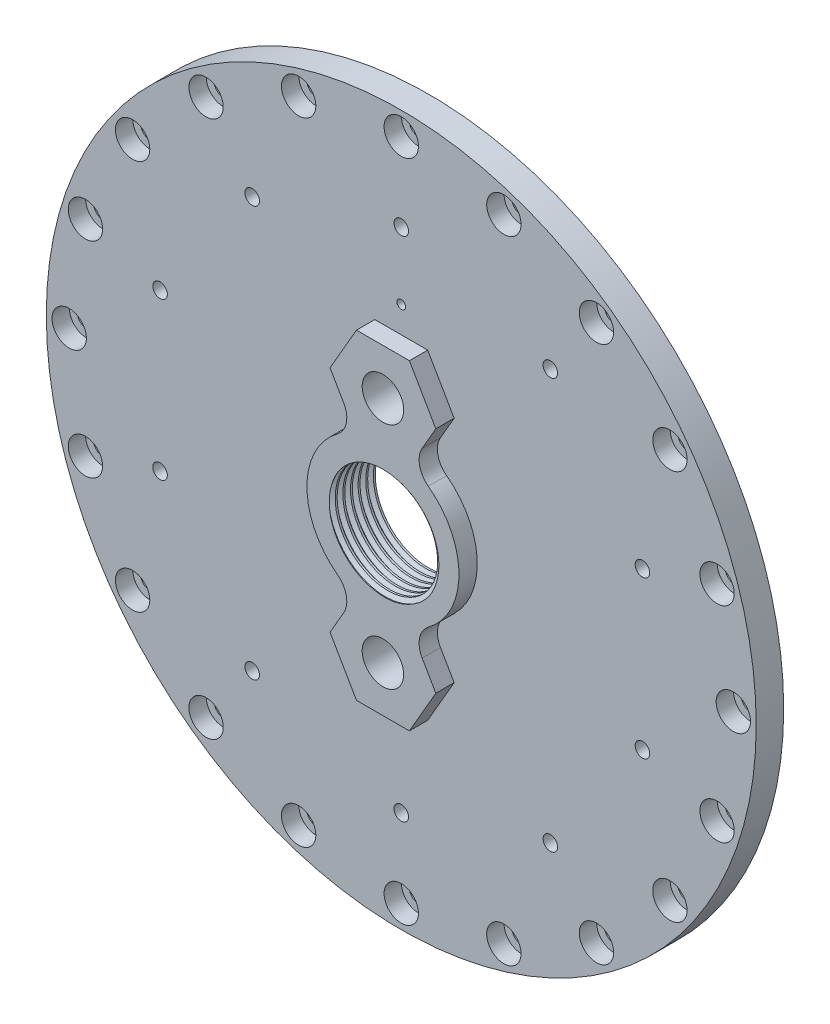
SolidWorks part; units mm, degrees
material "AISI 316 Stainless Steel Sheet (SS)"
ref_plane "Front Plane" through (0, 0, 0) normal (0, 0, 1) x (1, 0, 0)
ref_plane "Top Plane" through (0, 0, 0) normal (0, 1, 0) x (1, 0, 0)
ref_plane "Right Plane" through (0, 0, 0) normal (1, 0, 0) x (0, 0, -1)
sketch "Sketch1" plane through (0, 0, 0) normal (1, 0, 0) x (0, 0, -1)
  line L0 (0, 21.082) -> (0, 98.425)
  line L1 (0, 98.425) -> (7.62, 98.425)
  line L2 (7.62, 98.425) -> (7.62, 88.6333)
  line L3 (7.62, 83.82) -> (5.08, 83.82)
  line L4 (5.08, 83.82) -> (5.08, 56.8325)
  line L5 (5.08, 56.8325) -> (7.62, 56.8325)
  line L6 (7.62, 56.8325) -> (7.62, 53.0225)
  line L7 (7.62, 14.732) -> (-5.08, 14.732)
  line L8 (-5.08, 14.732) -> (-5.08, 21.082)
  line L9 (-5.08, 21.082) -> (0, 21.082)
  line L10 (0, 0) -> (59.2702, 0) construction
  line L12 (7.62, 49.6951) -> (6.2992, 49.6951)
  line L14 (7.62, 47.0535) -> (6.2992, 47.0535)
  line L15 (6.2992, 49.6951) -> (6.2992, 47.0535)
  line L20 (7.62, 47.0535) -> (7.62, 46.0375)
  line L21 (7.62, 85.1027) -> (7.62, 83.82)
  line L22 (7.62, 50.4825) -> (7.62, 49.6951)
  line L23 (7.62, 21.59) -> (7.62, 14.732)
  line L24 (7.62, 46.0375) -> (5.08, 46.0375)
  line L26 (7.62, 21.59) -> (5.08, 21.59)
  line L27 (5.08, 46.0375) -> (5.08, 21.59)
  line L28 (7.62, 53.0225) -> (6.35, 53.0225)
  line L32 (7.62, 50.4825) -> (6.35, 50.4825)
  line L33 (6.35, 53.0225) -> (6.35, 50.4825)
  line L35 (7.62, 88.6333) -> (5.6642, 88.6333)
  line L37 (7.62, 85.1027) -> (5.6642, 85.1027)
  line L38 (5.6642, 88.6333) -> (5.6642, 85.1027)
  point P19 (6.35, 51.7525)
  point P22 (6.2992, 48.3743)
  point P31 (5.6642, 86.868)
  dimension "D1" = 196.85
  dimension "D2" = 2.54
  dimension "D3" = 7.62
  dimension "D4" = 2.54
  dimension "D5" = 113.665
  dimension "D6" = 12.7
  dimension "D7" = 29.464
  dimension "D8" = 6.35
  dimension "D9" = 2.6416
  dimension "D10" = 96.7486
  dimension "D11" = 1.3208
  dimension "D12" = 167.64
  dimension "D13" = 92.075
  dimension "D14" = 43.18
  dimension "D15" = 1.27
  dimension "D16" = 2.54
  dimension "D17" = 103.505
  dimension "D18" = 1.9558
  dimension "D19" = 3.5306
  dimension "D20" = 173.736
revolve "Revolve1" add sketch "Sketch1" angle 360 about L10 region at (0, 54.7882, -2.7116)
thread "Thread1" pitch 2.1167 method cut profile "Thread Profile1" start angle 0, offset 4.318, length 0, pitch 2.1167, diameter 29.464
ref_plane "Plane1" through (-14.732, 0, 9.398) normal (0, -1, 0) x (-1, 0, 0)
sketch "Thread Profile1" plane through (-14.732, 0, 9.398) normal (0, -1, 0) x (-1, 0, 0)
  line L0 (0, 0) -> (0, 2.1167) construction
  line L1 (0, 0) -> (1.1457, 0.6615)
  line L2 (1.1457, 0.6615) -> (1.1457, 0.926)
  line L3 (1.1457, 0.926) -> (0, 1.5875)
  line L4 (1.1457, 0.7937) -> (0, 0.7937) construction
  line L11 (0, 0) -> (0, 1.5875)
  point P2 (0, 0)
  dimension "Pitch" = 2.1167
  dimension "Profile_Angle" = 60
  dimension "Profile_Land" = 0.2646
  dimension "Profile_Height" = 1.1457
sketch "Sketch15" plane through (0, 0, 0) normal (0, 0, 1) x (1, 0, 0)
  line L10 (0, 0) -> (104.8126, 0) construction
  line L11 (7.3323, 19.05) -> (14.6647, 31.75)
  line L12 (14.6647, 31.75) -> (7.3323, 44.45)
  line L13 (7.3323, 44.45) -> (-7.3323, 44.45)
  line L14 (-7.3323, 44.45) -> (-14.6647, 31.75)
  line L15 (-14.6647, 31.75) -> (-7.3323, 19.05)
  line L16 (-7.3323, 19.05) -> (7.3323, 19.05)
  line L17 (-7.3323, -19.05) -> (7.3323, -19.05)
  line L18 (-14.6647, -31.75) -> (-7.3323, -19.05)
  line L19 (-7.3323, -44.45) -> (-14.6647, -31.75)
  line L20 (7.3323, -44.45) -> (-7.3323, -44.45)
  line L21 (14.6647, -31.75) -> (7.3323, -44.45)
  line L22 (7.3323, -19.05) -> (14.6647, -31.75)
  circle A8 centre (0, 31.75) radius 12.7 construction
  circle A9 centre (0, -31.75) radius 12.7 construction
  dimension "D2" = 63.5
  dimension "D1" = 25.4
extrude "Boss-Extrude1" add sketch "Sketch15" along normal up to surface (5.08 mm away) up to face at (21.082, 0, 5.08)
hole_wizard "1/2-20 Tapped Hole2" positions "Sketch20" profile "Sketch17" tap size "1/2-20" standard "ANSI Inch" end condition through all
sketch "Sketch20" plane through (0, 0, 5.08) normal (0, 0, 1) x (1, 0, 0)
  point P9 (0, 31.75)
  point P16 (0, -31.75)
sketch "Sketch17" plane through (0, 31.75, 5.08) normal (1, 0, 0) x (0, -1, 0)
  line L0 (0, 0) -> (0, 13.4424)
  line L1 (0, 13.4424) -> (5.7544, 13.4424)
  line L2 (5.7544, 13.4424) -> (5.7544, 0)
  line L5 (5.7544, 0) -> (0, 0)
  line L11 (0, -6.35) -> (0, 107.95) construction
  dimension "Thru Tap Drill Dia." = 11.5087
  dimension "Thru Tap Drill Depth" = 13.4424
cosmetic thread "Hole Thread3" parameters "D2"=12.7
cosmetic thread "Hole Thread4" parameters "D2"=12.7
hole_wizard "CBORE for #10 Socket Head Cap Screw1" positions "Sketch19" profile "Sketch9" counterbore size "#10" standard "ANSI Inch" end condition up to next
sketch "Sketch19" plane through (0, 0, 0) normal (0, 0, 1) x (1, 0, 0)
  circle A0 centre (0, 0) radius 92.075 construction
  point P0 (0, 92.075)
  point P16 (28.4527, 87.5685)
  point P17 (54.1203, 74.4902)
  point P18 (74.4902, 54.1203)
  point P19 (87.5685, 28.4527)
  point P20 (92.075, 0)
  point P21 (87.5685, -28.4527)
  point P22 (74.4902, -54.1203)
  point P23 (54.1203, -74.4902)
  point P24 (28.4527, -87.5685)
  point P25 (0, -92.075)
  point P26 (-28.4527, -87.5685)
  point P27 (-54.1203, -74.4902)
  point P28 (-74.4902, -54.1203)
  point P29 (-87.5685, -28.4527)
  point P30 (-92.075, 0)
  point P31 (-87.5685, 28.4527)
  point P32 (-74.4902, 54.1203)
  point P33 (-54.1203, 74.4902)
  point P34 (-28.4527, 87.5685)
  dimension "D1" = 184.15
  dimension "D2" = 20
sketch "Sketch9" plane through (0, 92.075, 0) normal (1, 0, 0) x (0, -1, 0)
  line L0 (0, 0) -> (0, 7.62)
  line L1 (0, 7.62) -> (2.5527, 7.62)
  line L3 (2.5527, 7.62) -> (2.5527, 4.826)
  line L4 (2.5527, 4.826) -> (4.7625, 4.826)
  line L5 (4.7625, 4.826) -> (4.7625, 0)
  line L7 (4.7625, 0) -> (0, 0)
  line L11 (0, -6.35) -> (0, 107.95) construction
  dimension "Thru Hole Dia." = 5.1054
  dimension "Thru Hole Depth" = 7.62
  dimension "C'Bore Dia." = 9.525
  dimension "C'Bore Depth" = 4.826
fillet "Fillet1" radius 6.35 4 edges at (-7.6711, 19.6368, 2.54) (-7.6711, -19.6368, 2.54) (7.6711, -19.6368, 2.54) (7.6711, 19.6368, 2.54)
hole_wizard "3/32 (0.09375) Dowel Hole1" positions "Sketch23" profile "Sketch22" hole size "3/32" standard "ANSI Inch" end condition up to next
sketch "Sketch23" plane through (0, 0, -6.35) normal (0, 0, -1) x (-1, 0, 0)
  line L0 (0, 50.4825) -> (0, 53.0225) construction
  circle A1 centre (0, 0) radius 50.4825 construction
  circle A2 centre (0, 0) radius 53.0225 construction
  point P0 (0, 51.7525)
  point P15 (0, 51.7525)
sketch "Sketch22" plane through (0, 51.7525, -6.35) normal (1, 0, 0) x (0, 1, 0)
  line L0 (0, 0) -> (0, 6.35)
  line L1 (0, 6.35) -> (1.1906, 6.35)
  line L2 (1.1906, 6.35) -> (1.1906, 0)
  line L5 (1.1906, 0) -> (0, 0)
  line L11 (0, -6.35) -> (0, 107.95) construction
  dimension "Thru Hole Dia." = 2.3812
  dimension "Thru Hole Depth" = 6.35
sketch "Sketch24" plane through (0, 0, 0) normal (0, 0, 1) x (1, 0, 0)
  line L0 (0, 56.8325) -> (0, 83.82) construction
  line L2 (14.4037, 90.9414) -> (0, 0) construction
  circle A0 centre (0, 0) radius 70.3263 construction
  circle A1 centre (0, 0) radius 56.8325 construction
  circle A2 centre (0, 0) radius 56.8325 construction
  circle A3 centre (0, 0) radius 83.82 construction
  arc A4 (0, 92.075) -> (28.4527, 87.5685) centre (0, 0) cw construction
  circle A5 centre (0, 0) radius 92.075 construction
  point P0 (0, 70.3263)
  point P14 (0, 70.3263)
sketch "Sketch25" plane through (0, 0, 0) normal (0, 0, 1) x (1, 0, 0)
  point P0 (0, 70.3263)
hole_wizard "#10-32 Tapped Hole1" positions "Sketch25" profile "Sketch27" tap size "#10-32" standard "ANSI Inch"
sketch "Sketch27" plane through (0, 70.3263, 0) normal (1, 0, 0) x (0, -1, 0)
  line L0 (0, 0) -> (0, 4.318)
  line L1 (0, 4.318) -> (2.0193, 3.1047)
  line L2 (2.0193, 3.1047) -> (2.0193, 0)
  line L5 (2.0193, 0) -> (0, 0)
  line L10 (0, 4.318) -> (-2.0193, 3.1047) construction
  line L11 (0, -6.35) -> (0, 107.95) construction
  dimension "Tap Drill Dia." = 4.0386
  dimension "Tap Drill Depth" = 4.318
  dimension "Drill Angle" = 118
cosmetic thread "Hole Thread5" parameters "D1"=9.652, "D2"=4.826
pattern_circular "CirPattern1" count 10 over 360 about axis through (0, 0, 0) along (0, 0, 1) of "#10-32 Tapped Hole1" reverse direction yes
cosmetic thread "Hole Thread6" parameters "D1"=9.652, "D2"=4.826
cosmetic thread "Hole Thread7" parameters "D1"=9.652, "D2"=4.826
cosmetic thread "Hole Thread8" parameters "D1"=9.652, "D2"=4.826
cosmetic thread "Hole Thread9" parameters "D1"=9.652, "D2"=4.826
cosmetic thread "Hole Thread10" parameters "D1"=9.652, "D2"=4.826
cosmetic thread "Hole Thread11" parameters "D1"=9.652, "D2"=4.826
cosmetic thread "Hole Thread12" parameters "D1"=9.652, "D2"=4.826
cosmetic thread "Hole Thread13" parameters "D1"=9.652, "D2"=4.826
cosmetic thread "Hole Thread14" parameters "D1"=9.652, "D2"=4.826
